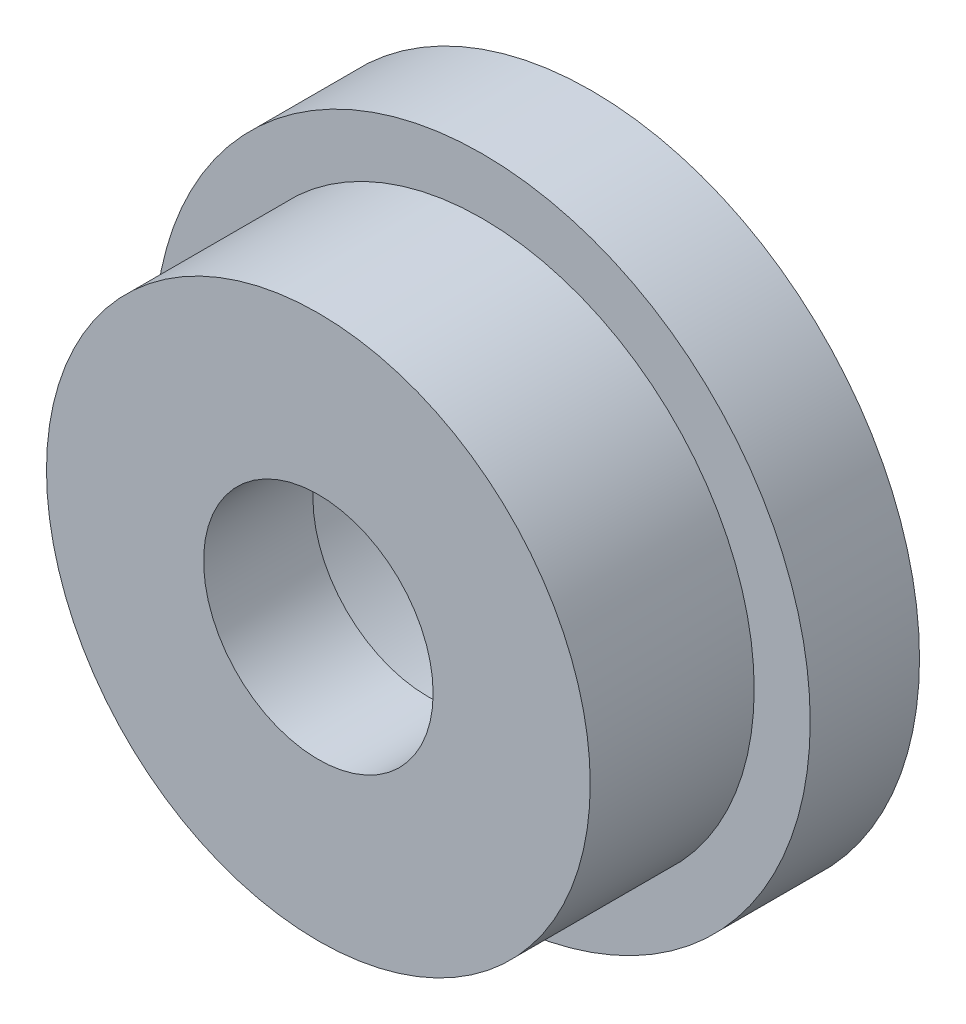
SolidWorks part; units mm, degrees
ref_plane "正面" through (0, 0, 0) normal (0, 0, 1) x (1, 0, 0)
ref_plane "平面" through (0, 0, 0) normal (0, 1, 0) x (1, 0, 0)
ref_plane "右側面" through (0, 0, 0) normal (1, 0, 0) x (0, 0, -1)
sketch "ｽｹｯﾁ1" plane through (0, 0, 0) normal (0, 0, 1) x (1, 0, 0)
  circle A0 centre (0, 0) radius 4.975
  dimension "D1" = 9.95
extrude "ﾎﾞｽ - 押し出し1" add sketch "ｽｹｯﾁ1" along normal blind 3
sketch "ｽｹｯﾁ2" plane through (0, 0, 0) normal (0, 0, -1) x (-1, 0, 0)
  circle A0 centre (0, 0) radius 6
  dimension "D1" = 12
extrude "ﾎﾞｽ - 押し出し2" add sketch "ｽｹｯﾁ2" along normal blind 2 contours A0
sketch "ｽｹｯﾁ3" plane through (0, 0, 3) normal (0, 0, 1) x (1, 0, 0)
  circle A0 centre (0, 0) radius 2.1
  dimension "D1" = 4.2
extrude "ｶｯﾄ - 押し出し1" cut sketch "ｽｹｯﾁ3" against normal through all
sketch "ｽｹｯﾁ4" plane through (0, 0, -2) normal (0, 0, -1) x (-1, 0, 0)
  circle A0 centre (0, 0) radius 4
  dimension "D1" = 8
extrude "ｶｯﾄ - 押し出し2" cut sketch "ｽｹｯﾁ4" against normal blind 3
